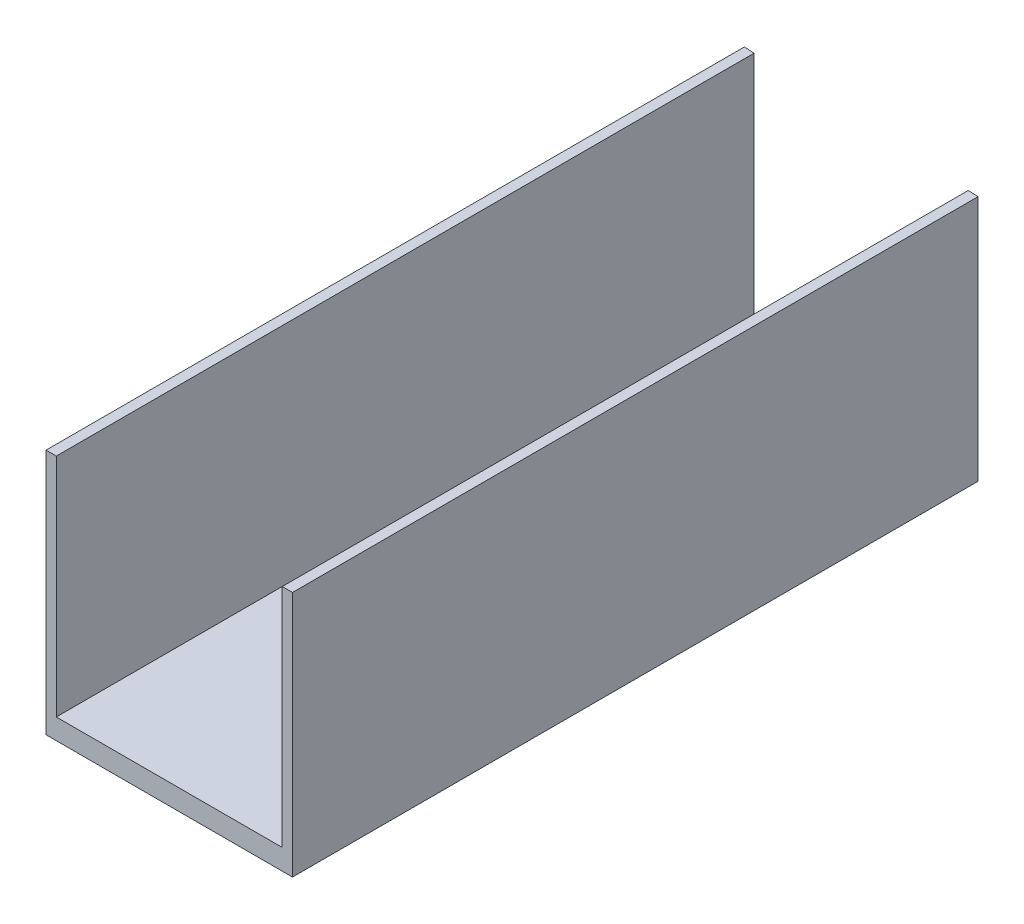
SolidWorks part; units mm, degrees
ref_plane "Front Plane" through (0, 0, 0) normal (0, 0, 1) x (1, 0, 0)
ref_plane "Top Plane" through (0, 0, 0) normal (0, 1, 0) x (1, 0, 0)
ref_plane "Right Plane" through (0, 0, 0) normal (1, 0, 0) x (0, 0, -1)
sketch "Sketch1" plane through (0, 0, 0) normal (0, 0, 1) x (1, 0, 0)
  line L0 (18.3712, 0) -> (-19.7288, 0)
  line L1 (-19.7288, 0) -> (-19.7288, 38.1)
  line L2 (-19.7288, 38.1) -> (-18.1413, 38.1)
  line L3 (-18.1413, 38.1) -> (-18.1413, 3.175)
  line L4 (-18.1413, 3.175) -> (16.7837, 3.175)
  line L5 (16.7837, 3.175) -> (16.7837, 38.1)
  line L6 (16.7837, 38.1) -> (18.3712, 38.1)
  line L7 (18.3712, 38.1) -> (18.3712, 0)
  dimension "D1" = 1.5875
  dimension "D2" = 1.5875
  dimension "D3" = 3.175
  dimension "D4" = 38.1
  dimension "D5" = 38.1
  dimension "D6" = 38.1
extrude "Boss-Extrude1" add sketch "Sketch1" along normal blind 107.95
sketch "Sketch2" plane through (0, 38.1, 0) normal (0, 1, 0) x (1, 0, 0)
  line L0 (-19.7288, 0) -> (18.3712, 0)
  line L1 (18.3712, 0) -> (18.3712, -1.9967)
  line L2 (18.3712, -107.95) -> (18.3712, 0) construction
  line L3 (18.3712, -1.9967) -> (-19.7288, 0)
  dimension "D1" = 3
extrude "Cut-Extrude1" cut sketch "Sketch2" against normal blind 98.425
